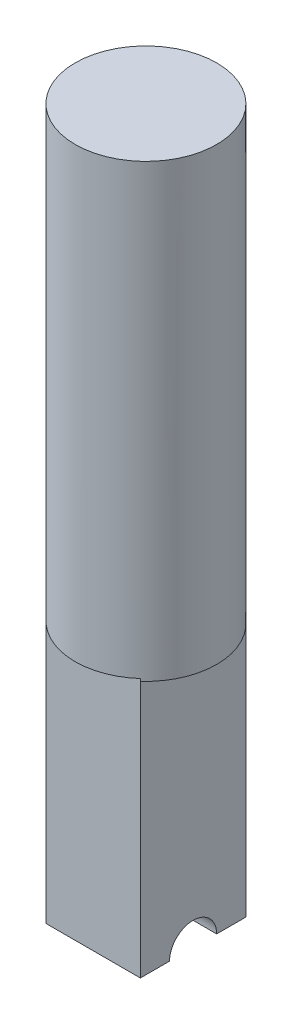
SolidWorks part; units mm, degrees
ref_plane "Front Plane" through (0, 0, 0) normal (0, 0, 1) x (1, 0, 0)
ref_plane "Top Plane" through (0, 0, 0) normal (0, 1, 0) x (1, 0, 0)
ref_plane "Right Plane" through (0, 0, 0) normal (1, 0, 0) x (0, 0, -1)
sketch "Sketch2" plane through (0, 0, 0) normal (0, 1, 0) x (1, 0, 0)
  circle A0 centre (0, 0) radius 15
  dimension "D1" = 30
extrude "Boss-Extrude1" add sketch "Sketch2" along normal blind 150
sketch "Sketch3" plane through (0, 0, 0) normal (1, 0, 0) x (0, 0, -1)
  line L0 (15, 0) -> (15, 150) construction
  line L1 (-15, -54.4944) -> (15, -54.4944)
  line L2 (-15, -54.4944) -> (-15, 54.4944)
  line L3 (-15, 54.4944) -> (15, 54.4944)
  line L4 (15, -54.4944) -> (15, 54.4944)
  line L5 (-15, -54.4944) -> (15, 54.4944) construction
  line L6 (-15, 54.4944) -> (15, -54.4944) construction
  point P0 (0, 0)
extrude "Cut-Extrude1" cut sketch "Sketch3" along normal blind 100 from offset 10
extrude "Cut-Extrude2" cut sketch "Sketch3<2>" against normal blind 100 from offset 10 offset against normal yes
sketch "Sketch3<2>" plane through (0, 0, 0) normal (1, 0, 0) x (0, 0, -1) same geometry as "Sketch3"
sketch "Sketch4" plane through (10, 0, 0) normal (1, 0, 0) x (0, 0, -1)
  line L0 (11.1803, 54.4944) -> (11.1803, 0) construction
  line L1 (11.1803, 0) -> (-11.1803, 0) construction
  circle A0 centre (0.0003, 0) radius 5
  dimension "D1" = 10
  dimension "D2" = 11.18
  dimension "D3" = 0
sketch "Sketch5" plane through (0, 0, 0) normal (0, -1, 0) x (1, 0, 0)
  line L1 (-10, 11.1803) -> (10, 11.1803)
  line L3 (-10, -11.1803) -> (10, -11.1803)
  arc A0 (-10, -11.1803) -> (10, -11.1803) centre (0, 0) ccw
  arc A1 (10, 11.1803) -> (-10, 11.1803) centre (0, 0) ccw
  point P0 (0, 0)
extrude "Cut-Extrude4" cut sketch "Sketch5" against normal blind 55
extrude "Cut-Extrude5" cut sketch "Sketch4" against normal through all contours A0
